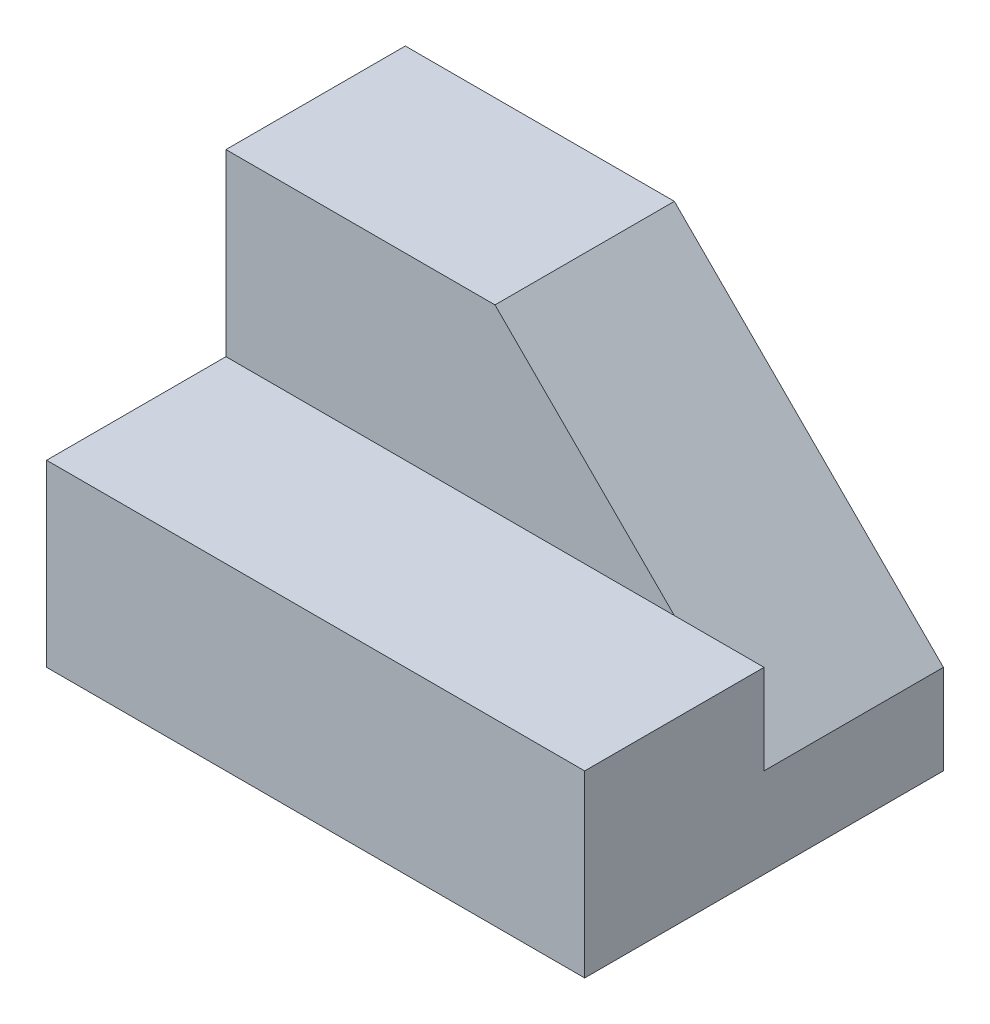
SolidWorks part; units mm, degrees
ref_plane "前基準面" through (0, 0, 0) normal (0, 0, 1) x (1, 0, 0)
ref_plane "上基準面" through (0, 0, 0) normal (0, 1, 0) x (1, 0, 0)
ref_plane "右基準面" through (0, 0, 0) normal (1, 0, 0) x (0, 0, -1)
sketch "草圖1" plane through (0, 0, 0) normal (0, 1, 0) x (1, 0, 0)
  line L1 (-15, 10) -> (15, 10)
  line L2 (-15, 10) -> (-15, -10)
  line L3 (-15, -10) -> (15, -10)
  line L4 (15, 10) -> (15, -10)
  line L5 (-15, 10) -> (15, -10) construction
  line L6 (-15, -10) -> (15, 10) construction
  line L7 (-15, 10) -> (0, 10)
  line L8 (-15, 10) -> (-15, 0)
  line L9 (-15, 0) -> (0, 0)
  line L10 (0, 10) -> (0, 0)
  line L11 (0, 0) -> (15, 0)
  line L12 (0, 0) -> (0, 10)
  line L13 (0, 10) -> (15, 10)
  line L14 (15, 0) -> (15, 10)
  point P0 (0, 0)
  dimension "D1" = 30
  dimension "D2" = 20
  dimension "D3" = 10
  dimension "D4" = 15
extrude "填料-伸長1" add sketch "草圖1" along normal blind 10 contours L10 L1 L2 L9 | L11 L9 L2 L3 L4 | L10 L11 L4 L1 region at (-7.5, 0, -5) region at (7.5, 0, -5) region at (0, 0, 5)
extrude "填料-伸長2" add sketch "草圖1<3>" along normal blind 20 contours L10 L1 L2 L9 | L10 L11 L4 L1 region at (-7.5, 0, -5) region at (7.5, 0, -5)
sketch "草圖1<3>" plane through (0, 0, 0) normal (0, 1, 0) x (1, 0, 0) same geometry as "草圖1"
sketch "草圖2" plane through (0, 0, -10) normal (0, 0, -1) x (-1, 0, 0)
  line L0 (-15, 5) -> (0, 20)
  line L1 (-15, 20) -> (-15, 0) construction
  line L2 (15, 20) -> (-15, 20) construction
  line L3 (0, 20) -> (-15, 20)
  line L4 (-15, 20) -> (-15, 5)
  dimension "D1" = 15
  dimension "D2" = 15
extrude "除料-伸長1" cut sketch "草圖2" against normal blind 10
